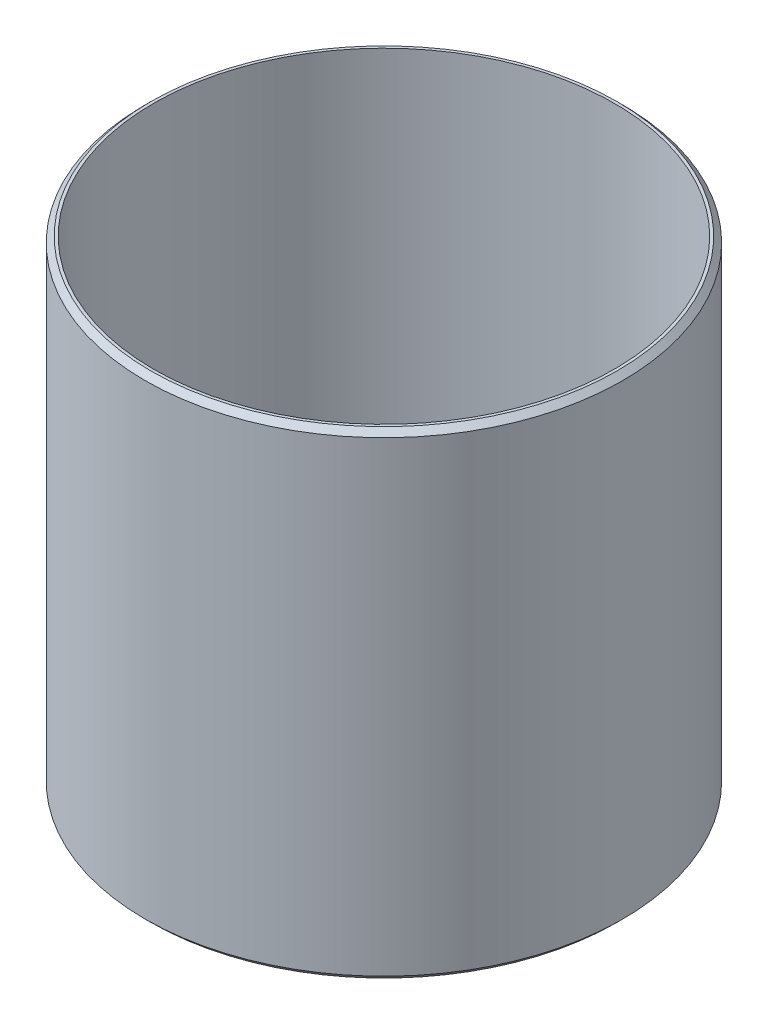
SolidWorks part; units mm, degrees
ref_plane "Front Plane" through (0, 0, 0) normal (0, 0, 1) x (1, 0, 0)
ref_plane "Top Plane" through (0, 0, 0) normal (0, 1, 0) x (1, 0, 0)
ref_plane "Right Plane" through (0, 0, 0) normal (1, 0, 0) x (0, 0, -1)
sketch "Sketch1" plane through (0, 0, 0) normal (0, 1, 0) x (1, 0, 0)
  circle A0 centre (0, 0) radius 81.9998
  circle A1 centre (0, 0) radius 84.9998
  dimension "D1" = 169.9997
  dimension "D2" = 3
extrude "Boss-Extrude1" add sketch "Sketch1" along normal blind 170
chamfer "Chamfer1" distance 2 angle 45 2 edges at (0, 0, 84.9998) (0, 170, 84.9998)
